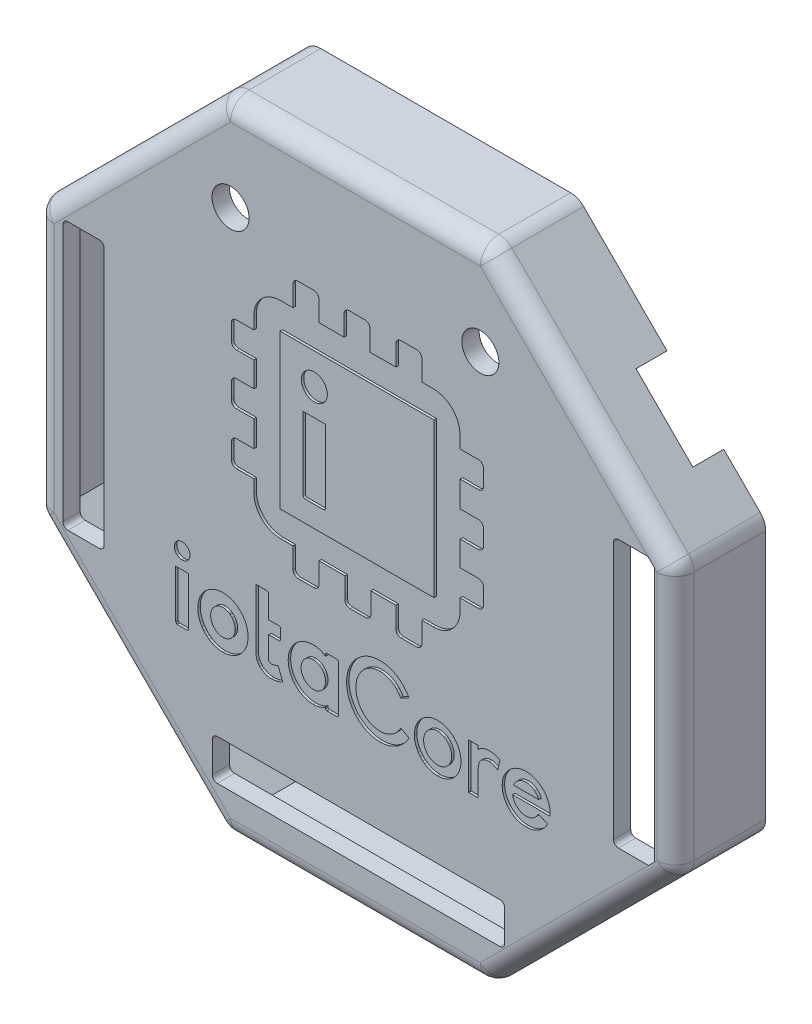
SolidWorks part; units mm, degrees
ref_plane "Front Plane" through (0, 0, 0) normal (0, 0, 1) x (1, 0, 0)
ref_plane "Top Plane" through (0, 0, 0) normal (0, 1, 0) x (1, 0, 0)
ref_plane "Right Plane" through (0, 0, 0) normal (1, 0, 0) x (0, 0, -1)
sketch "Sketch1" plane through (0, 0, 0) normal (0, 0, 1) x (1, 0, 0)
  line L0 (25.9, -10.1068) -> (25.9, 10.1068) construction
  line L1 (25.4607, 11.1675) -> (22.5059, 14.1222) construction
  line L2 (22.5059, 14.1222) -> (21.5159, 13.1323) construction
  line L3 (21.5159, 13.1323) -> (24.5, 10.1482) construction
  line L4 (24.5, 10.1482) -> (24.5, -10.1482) construction
  line L5 (24.5, -10.1482) -> (21.6927, -12.9555) construction
  line L6 (21.6927, -12.9555) -> (22.6827, -13.9455) construction
  line L7 (22.6827, -13.9455) -> (25.4607, -11.1675) construction
  line L8 (-16.1773, -20.4508) -> (-11.1675, -25.4607) construction
  line L9 (-10.1068, -25.9) -> (10.1068, -25.9) construction
  line L10 (11.1675, -25.4607) -> (15.6116, -21.0165) construction
  line L11 (15.6116, -21.0165) -> (14.6216, -20.0266) construction
  line L12 (14.6216, -20.0266) -> (10.1482, -24.5) construction
  line L13 (10.1482, -24.5) -> (-10.1482, -24.5) construction
  line L14 (-10.1482, -24.5) -> (-15.1873, -19.4609) construction
  line L15 (-15.1873, -19.4609) -> (-16.1773, -20.4508) construction
  line L16 (-22.117, 14.5112) -> (-25.4607, 11.1675) construction
  line L17 (-25.9, 10.1068) -> (-25.9, -10.1068) construction
  line L18 (-25.4607, -11.1675) -> (-22.1877, -14.4404) construction
  line L19 (-22.1877, -14.4404) -> (-21.1977, -13.4505) construction
  line L20 (-21.1977, -13.4505) -> (-24.5, -10.1482) construction
  line L21 (-24.5, -10.1482) -> (-24.5, 10.1482) construction
  line L22 (-24.5, 10.1482) -> (-21.127, 13.5212) construction
  line L23 (-21.127, 13.5212) -> (-22.117, 14.5112) construction
  line L24 (10.1068, 25.9) -> (-10.1068, 25.9) construction
  line L25 (-11.1675, 25.4607) -> (-17.5208, 19.1073) construction
  line L26 (-17.5208, 19.1073) -> (-16.5308, 18.1174) construction
  line L27 (-16.5308, 18.1174) -> (-10.1482, 24.5) construction
  line L28 (-10.1482, 24.5) -> (10.1482, 24.5) construction
  line L29 (10.1482, 24.5) -> (16.9197, 17.7285) construction
  line L30 (16.9197, 17.7285) -> (17.9097, 18.7184) construction
  line L31 (17.9097, 18.7184) -> (11.1675, 25.4607) construction
  line L32 (25.9, -10.1068) -> (25.9, 10.1068)
  line L33 (25.4607, 11.1675) -> (22.5059, 14.1222)
  line L34 (22.5059, 14.1222) -> (21.5159, 13.1323)
  line L35 (21.5159, 13.1323) -> (24.5, 10.1482)
  line L36 (24.5, 10.1482) -> (24.5, -10.1482)
  line L37 (24.5, -10.1482) -> (21.6927, -12.9555)
  line L38 (21.6927, -12.9555) -> (22.6827, -13.9455)
  line L39 (22.6827, -13.9455) -> (25.4607, -11.1675)
  line L40 (-16.1773, -20.4508) -> (-11.1675, -25.4607)
  line L41 (-10.1068, -25.9) -> (10.1068, -25.9)
  line L42 (11.1675, -25.4607) -> (15.6116, -21.0165)
  line L43 (15.6116, -21.0165) -> (14.6216, -20.0266)
  line L44 (14.6216, -20.0266) -> (10.1482, -24.5)
  line L45 (10.1482, -24.5) -> (-10.1482, -24.5)
  line L46 (-10.1482, -24.5) -> (-15.1873, -19.4609)
  line L47 (-15.1873, -19.4609) -> (-16.1773, -20.4508)
  line L48 (-22.117, 14.5112) -> (-25.4607, 11.1675)
  line L49 (-25.9, 10.1068) -> (-25.9, -10.1068)
  line L50 (-25.4607, -11.1675) -> (-22.1877, -14.4404)
  line L51 (-22.1877, -14.4404) -> (-21.1977, -13.4505)
  line L52 (-21.1977, -13.4505) -> (-24.5, -10.1482)
  line L53 (-24.5, -10.1482) -> (-24.5, 10.1482)
  line L54 (-24.5, 10.1482) -> (-21.127, 13.5212)
  line L55 (-21.127, 13.5212) -> (-22.117, 14.5112)
  line L56 (10.1068, 25.9) -> (-10.1068, 25.9)
  line L57 (-11.1675, 25.4607) -> (-17.5208, 19.1073)
  line L58 (-17.5208, 19.1073) -> (-16.5308, 18.1174)
  line L59 (-16.5308, 18.1174) -> (-10.1482, 24.5)
  line L60 (-10.1482, 24.5) -> (10.1482, 24.5)
  line L61 (10.1482, 24.5) -> (16.9197, 17.7285)
  line L62 (16.9197, 17.7285) -> (17.9097, 18.7184)
  line L63 (17.9097, 18.7184) -> (11.1675, 25.4607)
  line L66 (-17.5208, 19.1073) -> (-16.5308, 18.1174)
  line L67 (-21.127, 13.5212) -> (-22.117, 14.5112)
  arc A0 (25.9, 10.1068) -> (25.4607, 11.1675) centre (24.4, 10.1068) ccw construction
  arc A1 (25.4607, -11.1675) -> (25.9, -10.1068) centre (24.4, -10.1068) ccw construction
  arc A2 (-11.1675, -25.4607) -> (-10.1068, -25.9) centre (-10.1068, -24.4) ccw construction
  arc A3 (10.1068, -25.9) -> (11.1675, -25.4607) centre (10.1068, -24.4) ccw construction
  arc A4 (-25.4607, 11.1675) -> (-25.9, 10.1068) centre (-24.4, 10.1068) ccw construction
  arc A5 (-25.9, -10.1068) -> (-25.4607, -11.1675) centre (-24.4, -10.1068) ccw construction
  arc A6 (-10.1068, 25.9) -> (-11.1675, 25.4607) centre (-10.1068, 24.4) ccw construction
  arc A7 (11.1675, 25.4607) -> (10.1068, 25.9) centre (10.1068, 24.4) ccw construction
  arc A8 (25.9, 10.1068) -> (25.4607, 11.1675) centre (24.4, 10.1068) ccw
  arc A9 (25.4607, -11.1675) -> (25.9, -10.1068) centre (24.4, -10.1068) ccw
  arc A10 (-11.1675, -25.4607) -> (-10.1068, -25.9) centre (-10.1068, -24.4) ccw
  arc A11 (10.1068, -25.9) -> (11.1675, -25.4607) centre (10.1068, -24.4) ccw
  arc A12 (-25.4607, 11.1675) -> (-25.9, 10.1068) centre (-24.4, 10.1068) ccw
  arc A13 (-25.9, -10.1068) -> (-25.4607, -11.1675) centre (-24.4, -10.1068) ccw
  arc A14 (-10.1068, 25.9) -> (-11.1675, 25.4607) centre (-10.1068, 24.4) ccw
  arc A15 (11.1675, 25.4607) -> (10.1068, 25.9) centre (10.1068, 24.4) ccw
extrude "Boss-Extrude1" add sketch "Sketch1" along normal blind 5 contours L63 A15 L56 A14 L57 L58 L59 L60 L61 L62 | L49 A13 L50 L51 L52 L53 L54 L55 L48 A12 | L41 A11 L42 L43 L44 L45 L46 L47 L40 A10 | L39 A9 L32 A8 L33 L34 L35 L36 L37 L38 region at (24.747, 0.1144, 0) region at (-15.453, -20.1852, 0) region at (-24.631, 0.0454, 0) region at (10.5417, 25.4499, 0)
sketch "Sketch2" plane through (0, 0, 5) normal (0, 0, 1) x (1, 0, 0)
  line L0 (22.6827, -13.9455) -> (25.4607, -11.1675) construction
  line L1 (25.9, -10.1068) -> (25.9, 10.1068) construction
  line L2 (25.4607, 11.1675) -> (22.5059, 14.1222) construction
  line L3 (22.5059, 14.1222) -> (21.5159, 13.1323) construction
  line L4 (21.5159, 13.1323) -> (24.5, 10.1482) construction
  line L5 (24.5, 10.1482) -> (24.5, -10.1482) construction
  line L6 (24.5, -10.1482) -> (21.6927, -12.9555) construction
  line L7 (21.6927, -12.9555) -> (22.6827, -13.9455) construction
  line L8 (-10.1068, -25.9) -> (10.1068, -25.9) construction
  line L9 (11.1675, -25.4607) -> (15.6116, -21.0165) construction
  line L10 (15.6116, -21.0165) -> (14.6216, -20.0266) construction
  line L11 (14.6216, -20.0266) -> (10.1482, -24.5) construction
  line L12 (10.1482, -24.5) -> (-10.1482, -24.5) construction
  line L13 (-10.1482, -24.5) -> (-15.1873, -19.4609) construction
  line L14 (-15.1873, -19.4609) -> (-16.1773, -20.4508) construction
  line L15 (-16.1773, -20.4508) -> (-11.1675, -25.4607) construction
  line L16 (-25.9, 10.1068) -> (-25.9, -10.1068) construction
  line L17 (-25.4607, -11.1675) -> (-22.1877, -14.4404) construction
  line L18 (-22.1877, -14.4404) -> (-21.1977, -13.4505) construction
  line L19 (-21.1977, -13.4505) -> (-24.5, -10.1482) construction
  line L20 (-24.5, -10.1482) -> (-24.5, 10.1482) construction
  line L21 (-24.5, 10.1482) -> (-21.127, 13.5212) construction
  line L22 (-21.127, 13.5212) -> (-22.117, 14.5112) construction
  line L23 (-22.117, 14.5112) -> (-25.4607, 11.1675) construction
  line L24 (17.9097, 18.7184) -> (11.1675, 25.4607) construction
  line L25 (10.1068, 25.9) -> (-10.1068, 25.9) construction
  line L26 (-11.1675, 25.4607) -> (-17.5208, 19.1073) construction
  line L27 (-17.5208, 19.1073) -> (-16.5308, 18.1174) construction
  line L28 (-16.5308, 18.1174) -> (-10.1482, 24.5) construction
  line L29 (-10.1482, 24.5) -> (10.1482, 24.5) construction
  line L30 (10.1482, 24.5) -> (16.9197, 17.7285) construction
  line L31 (16.9197, 17.7285) -> (17.9097, 18.7184) construction
  line L32 (22.6827, -13.9455) -> (25.4607, -11.1675)
  line L33 (25.9, -10.1068) -> (25.9, 10.1068)
  line L34 (25.4607, 11.1675) -> (22.5059, 14.1222)
  line L35 (22.5059, 14.1222) -> (21.5159, 13.1323)
  line L36 (21.5159, 13.1323) -> (24.5, 10.1482)
  line L37 (24.5, 10.1482) -> (24.5, -10.1482)
  line L38 (24.5, -10.1482) -> (21.6927, -12.9555)
  line L39 (21.6927, -12.9555) -> (22.6827, -13.9455)
  line L40 (-10.1068, -25.9) -> (10.1068, -25.9)
  line L41 (11.1675, -25.4607) -> (15.6116, -21.0165)
  line L42 (15.6116, -21.0165) -> (14.6216, -20.0266)
  line L43 (14.6216, -20.0266) -> (10.1482, -24.5)
  line L44 (10.1482, -24.5) -> (-10.1482, -24.5)
  line L45 (-10.1482, -24.5) -> (-15.1873, -19.4609)
  line L46 (-15.1873, -19.4609) -> (-16.1773, -20.4508)
  line L47 (-16.1773, -20.4508) -> (-11.1675, -25.4607)
  line L48 (-25.9, 10.1068) -> (-25.9, -10.1068)
  line L49 (-25.4607, -11.1675) -> (-22.1877, -14.4404)
  line L50 (-22.1877, -14.4404) -> (-21.1977, -13.4505)
  line L51 (-21.1977, -13.4505) -> (-24.5, -10.1482)
  line L52 (-24.5, -10.1482) -> (-24.5, 10.1482)
  line L53 (-24.5, 10.1482) -> (-21.127, 13.5212)
  line L54 (-21.127, 13.5212) -> (-22.117, 14.5112)
  line L55 (-22.117, 14.5112) -> (-25.4607, 11.1675)
  line L56 (17.9097, 18.7184) -> (11.1675, 25.4607)
  line L57 (10.1068, 25.9) -> (-10.1068, 25.9)
  line L58 (-11.1675, 25.4607) -> (-17.5208, 19.1073)
  line L59 (-17.5208, 19.1073) -> (-16.5308, 18.1174)
  line L60 (-16.5308, 18.1174) -> (-10.1482, 24.5)
  line L61 (-10.1482, 24.5) -> (10.1482, 24.5)
  line L62 (10.1482, 24.5) -> (16.9197, 17.7285)
  line L63 (16.9197, 17.7285) -> (17.9097, 18.7184)
  line L64 (-22.117, 14.5112) -> (-17.5208, 19.1073)
  line L65 (-16.5308, 18.1174) -> (-21.127, 13.5212)
  line L66 (-21.1977, -13.4505) -> (-15.1873, -19.4609)
  line L67 (-16.1773, -20.4508) -> (-22.1877, -14.4404)
  line L68 (14.6216, -20.0266) -> (21.6927, -12.9555)
  line L69 (22.6827, -13.9455) -> (15.6116, -21.0165)
  line L70 (22.5059, 14.1222) -> (17.9097, 18.7184)
  line L71 (21.5159, 13.1323) -> (16.9197, 17.7285)
  arc A0 (25.4607, -11.1675) -> (25.9, -10.1068) centre (24.4, -10.1068) ccw construction
  arc A1 (25.9, 10.1068) -> (25.4607, 11.1675) centre (24.4, 10.1068) ccw construction
  arc A2 (10.1068, -25.9) -> (11.1675, -25.4607) centre (10.1068, -24.4) ccw construction
  arc A3 (-11.1675, -25.4607) -> (-10.1068, -25.9) centre (-10.1068, -24.4) ccw construction
  arc A4 (-25.9, -10.1068) -> (-25.4607, -11.1675) centre (-24.4, -10.1068) ccw construction
  arc A5 (-25.4607, 11.1675) -> (-25.9, 10.1068) centre (-24.4, 10.1068) ccw construction
  arc A6 (11.1675, 25.4607) -> (10.1068, 25.9) centre (10.1068, 24.4) ccw construction
  arc A7 (-10.1068, 25.9) -> (-11.1675, 25.4607) centre (-10.1068, 24.4) ccw construction
  arc A8 (25.4607, -11.1675) -> (25.9, -10.1068) centre (24.4, -10.1068) ccw
  arc A9 (25.9, 10.1068) -> (25.4607, 11.1675) centre (24.4, 10.1068) ccw
  arc A10 (10.1068, -25.9) -> (11.1675, -25.4607) centre (10.1068, -24.4) ccw
  arc A11 (-11.1675, -25.4607) -> (-10.1068, -25.9) centre (-10.1068, -24.4) ccw
  arc A12 (-25.9, -10.1068) -> (-25.4607, -11.1675) centre (-24.4, -10.1068) ccw
  arc A13 (-25.4607, 11.1675) -> (-25.9, 10.1068) centre (-24.4, 10.1068) ccw
  arc A14 (11.1675, 25.4607) -> (10.1068, 25.9) centre (10.1068, 24.4) ccw
  arc A15 (-10.1068, 25.9) -> (-11.1675, 25.4607) centre (-10.1068, 24.4) ccw
  line M21 (17.9097, 18.7184) -> (11.1675, 25.4607)
  arc M22 (11.1675, 25.4607) -> (10.1068, 25.9) centre (10.1068, 24.4) ccw
  line M23 (10.1068, 25.9) -> (-10.1068, 25.9)
  arc M24 (-10.1068, 25.9) -> (-11.1675, 25.4607) centre (-10.1068, 24.4) ccw
  line M25 (-11.1675, 25.4607) -> (-17.5208, 19.1073)
  line M26 (-17.5208, 19.1073) -> (-16.5308, 18.1174)
  line M27 (-16.5308, 18.1174) -> (-10.1482, 24.5)
  line M28 (-10.1482, 24.5) -> (10.1482, 24.5)
  line M29 (10.1482, 24.5) -> (16.9197, 17.7285)
  line M30 (16.9197, 17.7285) -> (17.9097, 18.7184)
extrude "Boss-Extrude2" add sketch "Sketch2" along normal blind 1.4 contours L36 L71 L65 L53 L52 L51 L66 L45 L44 L43 L68 L38 L37 M29 M28 M27 | L33 A9 L34 L35 L36 L37 L38 L39 L32 A8 | L69 L39 L68 L42 | L47 A11 L40 A10 L41 L42 L43 L44 L45 L46 | L67 L46 L66 L50 | L55 A13 L48 A12 L49 L50 L51 L52 L53 L54 | L65 L64 L54 M26 | M30 M21 M22 M23 M24 M25 M26 M27 M28 M29 | L71 L35 L70 M30 region at (24.747, 0.1144, 5) region at (18.6522, -16.986, 5) region at (0, 0, 5) region at (13.1602, -23.0093, 5) region at (19.7128, 15.9254, 5) region at (13.7911, 21.3714, 5) region at (-18.6875, -16.9507, 5) region at (-24.631, 0.0454, 5) region at (-19.3239, 16.3143, 5)
sketch "Sketch3" plane through (0, 0, 5) normal (0, 0, -1) x (-1, 0, 0)
  line L0 (-21.5159, 13.1323) -> (-16.9197, 17.7285)
  line L1 (-16.9197, 17.7285) -> (-17.9097, 18.7184)
  line L2 (-17.9097, 18.7184) -> (-22.5059, 14.1222)
  line L3 (-22.5059, 14.1222) -> (-21.5159, 13.1323)
  line L4 (21.127, 13.5212) -> (16.5308, 18.1174)
  line L5 (16.5308, 18.1174) -> (17.5208, 19.1073)
  line L6 (17.5208, 19.1073) -> (22.117, 14.5112)
  line L7 (22.117, 14.5112) -> (21.127, 13.5212)
extrude "Boss-Extrude3" add sketch "Sketch3" along normal blind 3.4 contours L7 L4 L5 L6 | L3 L0 L1 L2
sketch "Sketch4" plane through (0, 0, 5) normal (0, 0, -1) x (-1, 0, 0)
  line L0 (-15.6116, -21.0165) -> (-14.6216, -20.0266)
  line L1 (-14.6216, -20.0266) -> (-21.6927, -12.9555)
  line L2 (-21.6927, -12.9555) -> (-22.6827, -13.9455)
  line L3 (-22.6827, -13.9455) -> (-15.6116, -21.0165)
extrude "Boss-Extrude4" add sketch "Sketch4" along normal blind 3.4
sketch "Sketch5" plane through (0, 0, 5) normal (0, 0, -1) x (-1, 0, 0)
  line L0 (16.1773, -20.4508) -> (22.1877, -14.4404)
  line L1 (22.1877, -14.4404) -> (21.1977, -13.4505)
  line L2 (21.1977, -13.4505) -> (15.1873, -19.4609)
  line L3 (15.1873, -19.4609) -> (16.1773, -20.4508)
extrude "Boss-Extrude5" add sketch "Sketch5" along normal blind 1
fillet "Fillet1" radius 1.5 18 edges at (10.6808, -25.7858, 6.4) (0, -25.9, 6.4) (-10.6808, -25.7858, 6.4) (-18.3141, -18.3141, 6.4) (-25.7858, -10.6808, 6.4) (-25.9, 0, 6.4) (-25.7858, 10.6808, 6.4) (-18.3141, 18.3141, 6.4) (-10.6808, 25.7858, 6.4) (0, 25.9, 6.4) (10.6808, 25.7858, 6.4) (18.3141, 18.3141, 6.4) (25.7858, 10.6808, 6.4) (25.9, 0, 6.4) (25.7858, -10.6808, 6.4) (18.3141, -18.3141, 6.4) (15.1166, -20.5216, 1.6) (22.1877, -13.4505, 1.6)
sketch "Sketch6" plane through (0, 0, 6.4) normal (0, 0, 1) x (1, 0, 0)
  line L0 (-23.2729, -10.394) -> (-20.7329, -10.394) construction
  line L1 (-23.2729, 10.434) -> (-23.2729, -10.394) construction
  line L2 (-20.7329, -10.394) -> (-20.7329, 10.434) construction
  line L3 (-20.7329, 10.434) -> (-23.2729, 10.434) construction
  line L4 (21.2779, -10.389) -> (23.8179, -10.389) construction
  line L5 (23.8179, -10.389) -> (23.8179, 10.439) construction
  line L6 (21.2779, 10.439) -> (21.2779, -10.389) construction
  line L7 (23.8179, 10.439) -> (21.2779, 10.439) construction
  line L8 (-23.2729, -10.394) -> (-20.7329, -10.394)
  line L9 (-23.2729, 10.434) -> (-23.2729, -10.394)
  line L10 (-20.7329, -10.394) -> (-20.7329, 10.434)
  line L11 (-20.7329, 10.434) -> (-23.2729, 10.434)
  line L12 (21.2779, -10.389) -> (23.8179, -10.389)
  line L13 (23.8179, -10.389) -> (23.8179, 10.439)
  line L14 (21.2779, 10.439) -> (21.2779, -10.389)
  line L15 (23.8179, 10.439) -> (21.2779, 10.439)
  line L16 (-20.3329, -10.394) -> (-20.3329, 10.434)
  line L17 (-20.7329, 10.834) -> (-23.2729, 10.834)
  line L18 (-23.6729, 10.434) -> (-23.6729, -10.394)
  line L19 (-23.2729, -10.794) -> (-20.7329, -10.794)
  line L20 (21.2779, -10.789) -> (23.8179, -10.789)
  line L21 (24.2179, -10.389) -> (24.2179, 10.439)
  line L22 (23.8179, 10.839) -> (21.2779, 10.839)
  line L23 (20.8779, 10.439) -> (20.8779, -10.389)
  line L24 (24.2179, 10.839) -> (20.8779, 10.839) construction
  line L25 (20.8779, 10.839) -> (20.8779, -10.789) construction
  line L26 (24.2179, -10.789) -> (24.2179, 10.839) construction
  line L27 (20.8779, -10.789) -> (24.2179, -10.789) construction
  line L28 (-20.3329, -10.794) -> (-20.3329, 10.834) construction
  line L29 (-23.6729, -10.794) -> (-20.3329, -10.794) construction
  line L30 (-23.6729, 10.834) -> (-23.6729, -10.794) construction
  line L31 (-20.3329, 10.834) -> (-23.6729, 10.834) construction
  arc A0 (21.2779, 10.839) -> (20.8779, 10.439) centre (21.2779, 10.439) ccw
  arc A1 (24.2179, 10.439) -> (23.8179, 10.839) centre (23.8179, 10.439) ccw
  arc A2 (23.8179, -10.789) -> (24.2179, -10.389) centre (23.8179, -10.389) ccw
  arc A3 (21.2779, -10.789) -> (20.8779, -10.389) centre (21.2779, -10.389) cw
  arc A4 (-20.3329, -10.394) -> (-20.7329, -10.794) centre (-20.7329, -10.394) cw
  arc A5 (-23.6729, -10.394) -> (-23.2729, -10.794) centre (-23.2729, -10.394) ccw
  arc A6 (-20.3329, 10.434) -> (-20.7329, 10.834) centre (-20.7329, 10.434) ccw
  arc A7 (-23.2729, 10.834) -> (-23.6729, 10.434) centre (-23.2729, 10.434) ccw
  line M15 (10.1068, -24.4) -> (24.4, -10.1068)
  line M17 (24.4, 10.1068) -> (10.1068, 24.4)
  dimension "D2" = 0.4
  dimension "D1" = 0.4
extrude "Cut-Extrude1" cut sketch "Sketch6" against normal through all contours L10 L11 L9 L8 | L17 A7 L18 A5 L19 A4 L16 A6 L11 L10 L8 L9 | L13 L15 L14 L12 | A3 L20 L21 L22 A0 L23 L15 L13 L12 L14 M15 M17 region at (-22.0029, 0.02, 6.4) region at (22.5479, 0.025, 6.4) region at (-20.6048, -10.5221, 6.4) region at (21.1499, -10.5171, 6.4)
sketch "Sketch7" plane through (0, 0, 6.4) normal (0, 0, 1) x (1, 0, 0)
  line L0 (9.3915, -22.0846) -> (11.6775, -22.0846) construction
  line L1 (11.6775, -22.0846) -> (11.6775, -19.5954) construction
  line L2 (-11.1825, -22.0846) -> (-8.8965, -22.0846) construction
  line L3 (-11.1825, -19.5954) -> (-11.1825, -22.0846) construction
  line L4 (9.3915, -22.0846) -> (11.6775, -22.0846)
  line L5 (11.6775, -22.0846) -> (11.6775, -19.5954)
  line L6 (-11.1825, -22.0846) -> (-8.8965, -22.0846)
  line L7 (-11.1825, -19.5954) -> (-11.1825, -22.0846)
  line L8 (-11.1825, -19.5954) -> (11.6775, -19.5954)
  line L9 (9.3915, -22.0846) -> (-8.8965, -22.0846)
  line L10 (9.3915, -22.4846) -> (-8.8965, -22.4846)
  line L11 (-11.1825, -22.4846) -> (-8.8965, -22.4846)
  line L12 (-11.5825, -19.5954) -> (-11.5825, -22.0846)
  line L13 (-11.1825, -19.1954) -> (11.6775, -19.1954)
  line L14 (12.0775, -22.0846) -> (12.0775, -19.5954)
  line L15 (9.3915, -22.4846) -> (11.6775, -22.4846)
  line L16 (-11.5825, -19.1954) -> (12.0775, -19.1954) construction
  line L17 (12.0775, -22.4846) -> (12.0775, -19.1954) construction
  line L18 (9.3915, -22.4846) -> (12.0775, -22.4846) construction
  line L19 (-11.5825, -22.4846) -> (-8.8965, -22.4846) construction
  line L20 (-11.5825, -19.1954) -> (-11.5825, -22.4846) construction
  arc A0 (11.6775, -19.1954) -> (12.0775, -19.5954) centre (11.6775, -19.5954) cw
  arc A1 (12.0775, -22.0846) -> (11.6775, -22.4846) centre (11.6775, -22.0846) cw
  arc A2 (-11.1825, -22.4846) -> (-11.5825, -22.0846) centre (-11.1825, -22.0846) cw
  arc A3 (-11.5825, -19.5954) -> (-11.1825, -19.1954) centre (-11.1825, -19.5954) cw
  dimension "D2" = 0.4
  dimension "D1" = 0.4
extrude "Cut-Extrude2" cut sketch "Sketch7" against normal through all contours L9 L4 L5 L8 L7 L6 | A3 L12 A2 L11 L10 L15 A1 L14 A0 L13 L4 L9 L6 L7 L8 L5 | L9 L6 L7 L8 L5 L4 | L10 L11 A2 L12 A3 L13 A0 L14 A1 L15 region at (0.2475, -20.84, 6.4) region at (0.2475, -22.2457, 6.4)
sketch "Sketch10" plane through (0, 0, 6.4) normal (0, 0, 1) x (1, 0, 0)
  line L0 (6.3526, -0.709) -> (-6.1073, -0.709)
  line L1 (-6.1073, -0.709) -> (-6.1073, 11.751)
  line L2 (-6.1073, 11.751) -> (6.3526, 11.751)
  line L3 (6.3526, 11.751) -> (6.3526, -0.709)
  line L4 (10.3637, 9.084) -> (10.3637, 10.3555)
  line L5 (9.9467, 10.7717) -> (8.4679, 10.7717)
  line L6 (8.4679, 10.7717) -> (8.4679, 11.7461)
  line L7 (6.3004, 13.9128) -> (5.3733, 13.9128)
  line L8 (5.3733, 13.9128) -> (5.3733, 15.5588)
  line L9 (4.9563, 15.9758) -> (3.6857, 15.9758)
  line L10 (3.2686, 15.5588) -> (3.2686, 13.9128)
  line L11 (3.2686, 13.9128) -> (1.1746, 13.9128)
  line L12 (1.1746, 13.9128) -> (1.1746, 15.5588)
  line L13 (0.7584, 15.9758) -> (-0.5131, 15.9758)
  line L14 (-0.9293, 15.5588) -> (-0.9293, 13.9128)
  line L15 (-0.9293, 13.9128) -> (-2.9507, 13.9128)
  line L16 (-2.9507, 13.9128) -> (-2.9507, 15.5588)
  line L17 (-3.3678, 15.9758) -> (-4.6384, 15.9758)
  line L18 (-5.0554, 15.5588) -> (-5.0554, 13.9128)
  line L19 (-5.0554, 13.9128) -> (-6.0551, 13.9128)
  line L20 (-8.2226, 11.7461) -> (-8.2226, 10.7717)
  line L21 (-8.2226, 10.7717) -> (-9.6287, 10.7717)
  line L22 (-10.0458, 10.3555) -> (-10.0458, 9.084)
  line L23 (-9.6287, 8.6678) -> (-8.2226, 8.6678)
  line L24 (-8.2226, 8.6678) -> (-8.2226, 6.6463)
  line L25 (-8.2226, 6.6463) -> (-9.6287, 6.6463)
  line L26 (-10.0458, 6.2293) -> (-10.0458, 4.9587)
  line L27 (-9.6287, 4.5417) -> (-8.2226, 4.5417)
  line L28 (-8.2226, 4.5417) -> (-8.2226, 2.4476)
  line L29 (-8.2226, 2.4476) -> (-9.6287, 2.4476)
  line L30 (-10.0458, 2.0314) -> (-10.0458, 0.7599)
  line L31 (-9.6287, 0.3437) -> (-8.2226, 0.3437)
  line L32 (-8.2226, 0.3437) -> (-8.2226, -0.6095)
  line L33 (-6.0551, -2.777) -> (-5.0554, -2.777)
  line L34 (-5.0554, -2.777) -> (-5.0554, -4.4434)
  line L35 (-4.6384, -4.8604) -> (-3.3678, -4.8604)
  line L36 (-2.9507, -4.4434) -> (-2.9507, -2.777)
  line L37 (-2.9507, -2.777) -> (-0.8567, -2.777)
  line L38 (-0.8567, -2.777) -> (-0.8567, -4.4434)
  line L39 (-0.4396, -4.8604) -> (0.831, -4.8604)
  line L40 (1.248, -4.4434) -> (1.248, -2.777)
  line L41 (1.248, -2.777) -> (3.2686, -2.777)
  line L42 (3.2686, -2.777) -> (3.2686, -4.4434)
  line L43 (3.6857, -4.8604) -> (4.9563, -4.8604)
  line L44 (5.3733, -4.4434) -> (5.3733, -2.777)
  line L45 (5.3733, -2.777) -> (6.3004, -2.777)
  line L46 (8.4679, -0.6095) -> (8.4679, 0.3437)
  line L47 (8.4679, 0.3437) -> (9.9467, 0.3437)
  line L48 (10.3637, 0.7599) -> (10.3637, 2.0314)
  line L49 (9.9467, 2.4476) -> (8.4679, 2.4476)
  line L50 (8.4679, 2.4476) -> (8.4679, 4.469)
  line L51 (8.4679, 4.469) -> (9.9467, 4.469)
  line L52 (10.3637, 4.8861) -> (10.3637, 6.1567)
  line L53 (9.9467, 6.5737) -> (8.4679, 6.5737)
  line L54 (8.4679, 6.5737) -> (8.4679, 8.6678)
  line L55 (8.4679, 8.6678) -> (9.9467, 8.6678)
  line L56 (-2.4121, 7.0577) -> (-2.4121, 1.1786)
  line L57 (-2.5949, 0.9966) -> (-4.0639, 0.9966)
  line L58 (-4.2459, 1.1786) -> (-4.2459, 7.0577)
  line L59 (-4.2459, 7.0577) -> (-2.4121, 7.0577)
  line L60 (-14.5424, -8.9455) -> (-13.4977, -8.9455)
  line L61 (-13.4977, -8.9455) -> (-13.4977, -12.8799)
  line L62 (-13.4977, -12.8799) -> (-13.5822, -12.9643)
  line L63 (-13.5822, -12.9643) -> (-13.6459, -12.9681)
  line L64 (-13.6459, -12.9681) -> (-14.455, -12.9681)
  line L65 (-14.455, -12.9681) -> (-14.5385, -12.8827)
  line L66 (-14.5385, -12.8827) -> (-14.5424, -12.8198)
  line L67 (-14.5424, -12.8198) -> (-14.5424, -8.9455)
  line L68 (-13.3848, -7.597) -> (-13.3848, -7.6205)
  line L69 (-13.5529, -8.0427) -> (-13.561, -8.0512)
  line L70 (-14.0085, -8.2442) -> (-14.0319, -8.2442)
  line L71 (-14.4569, -8.0698) -> (-14.4636, -8.0631)
  line L72 (-14.6556, -7.6244) -> (-14.6556, -7.5931)
  line L73 (-14.4729, -7.16) -> (-14.4615, -7.1491)
  line L74 (-14.4615, -7.1491) -> (-14.3878, -7.0868)
  line L75 (-14.0358, -6.9733) -> (-14.0045, -6.9733)
  line L76 (-13.5861, -7.1413) -> (-13.5777, -7.1494)
  line L77 (-10.1353, -10.1363) -> (-10.155, -10.1279)
  line L78 (-10.155, -10.1279) -> (-10.1658, -10.1173)
  line L79 (-11.5056, -10.3384) -> (-11.5158, -10.355)
  line L80 (-11.3171, -11.8101) -> (-11.308, -11.8164)
  line L81 (-9.731, -10.9843) -> (-9.731, -10.9723)
  line L82 (-10.7052, -13.0616) -> (-10.7404, -13.0616)
  line L83 (-11.8353, -12.727) -> (-11.8441, -12.721)
  line L84 (-12.7555, -11.0036) -> (-12.7555, -10.9452)
  line L85 (-12.1524, -9.4873) -> (-12.1438, -9.4789)
  line L86 (-9.2496, -9.5351) -> (-9.2455, -9.5393)
  line L87 (-5.8737, -12.7382) -> (-6.0038, -12.793)
  line L88 (-6.8004, -12.9678) -> (-6.8082, -12.9678)
  line L89 (-7.7454, -12.5779) -> (-7.7604, -12.5614)
  line L90 (-7.7604, -12.5614) -> (-7.8266, -12.4749)
  line L91 (-8.0594, -11.7521) -> (-8.0594, -6.9733)
  line L92 (-8.0594, -6.9733) -> (-7.1072, -6.9733)
  line L93 (-7.1072, -6.9733) -> (-7.0226, -7.0577)
  line L94 (-7.0226, -7.0577) -> (-7.0187, -7.1213)
  line L95 (-7.0187, -7.1213) -> (-7.0187, -8.942)
  line L96 (-7.0187, -8.942) -> (-6.1361, -8.942)
  line L97 (-6.1361, -8.942) -> (-6.0512, -9.0261)
  line L98 (-6.0512, -9.0261) -> (-6.0474, -9.09)
  line L99 (-6.0474, -9.09) -> (-6.0474, -9.8979)
  line L100 (-6.0474, -9.8979) -> (-6.1319, -9.9827)
  line L101 (-6.1319, -9.9827) -> (-6.1954, -9.9865)
  line L102 (-6.1954, -9.9865) -> (-7.0187, -9.9865)
  line L103 (-7.0187, -9.9865) -> (-7.0187, -11.7243)
  line L104 (-6.4276, -11.8375) -> (-6.2631, -11.7573)
  line L105 (-6.2631, -11.7573) -> (-5.8737, -12.7382)
  line L106 (-3.3843, -9.9317) -> (-3.4467, -9.9317)
  line L107 (-3.4544, -12.0171) -> (-3.3686, -12.0171)
  line L108 (-1.377, -9.038) -> (-1.377, -12.876)
  line L109 (-1.377, -12.876) -> (-1.4692, -12.9681)
  line L110 (-1.4692, -12.9681) -> (-2.309, -12.9681)
  line L111 (-2.309, -12.9681) -> (-2.4215, -12.8936)
  line L112 (-2.4215, -12.8936) -> (-2.4215, -12.7611)
  line L113 (-3.3998, -13.0616) -> (-3.4036, -13.0616)
  line L114 (-2.4215, -9.2039) -> (-2.4215, -9.0201)
  line L115 (-2.4215, -9.0201) -> (-2.309, -8.9455)
  line L116 (-2.309, -8.9455) -> (-1.4692, -8.9455)
  line L117 (-1.4692, -8.9455) -> (-1.377, -9.038)
  line L118 (4.3331, -11.5371) -> (4.3331, -11.5529)
  line L119 (-0.7141, -10.1572) -> (-0.7141, -10.134)
  line L120 (1.979, -7.2927) -> (1.9868, -7.2927)
  line L121 (1.9516, -12.2427) -> (2.0335, -12.2427)
  line L122 (3.6746, -11.1905) -> (4.3331, -11.5371)
  line L123 (7.7893, -11.1107) -> (7.7893, -11.0991)
  line L124 (6.671, -13.0439) -> (6.6358, -13.0439)
  line L125 (4.7648, -11.13) -> (4.7648, -11.0716)
  line L126 (11.6934, -9.4189) -> (11.6934, -9.4228)
  line L127 (10.8514, -9.953) -> (10.7892, -9.953)
  line L128 (9.9159, -11.2196) -> (9.9159, -12.9349)
  line L129 (9.9159, -12.9349) -> (9.9082, -12.9465)
  line L130 (9.9082, -12.9465) -> (9.179, -12.9465)
  line L131 (9.179, -12.9465) -> (9.1674, -12.9349)
  line L132 (9.1674, -12.9349) -> (9.1674, -9.2748)
  line L133 (9.1674, -9.2748) -> (9.179, -9.2671)
  line L134 (9.179, -9.2671) -> (9.9082, -9.2671)
  line L135 (9.9082, -9.2671) -> (9.9159, -9.2748)
  line L136 (9.9159, -9.2748) -> (9.9159, -9.5553)
  line L137 (10.7966, -9.1929) -> (10.8943, -9.1929)
  line L138 (12.8553, -10.4754) -> (12.7878, -10.6195)
  line L139 (12.7878, -10.6195) -> (14.8381, -10.6195)
  line L140 (14.8381, -10.6195) -> (14.8381, -10.6157)
  line L141 (15.7554, -11.1029) -> (15.7554, -11.22)
  line L142 (15.7385, -11.329) -> (12.7115, -11.329)
  line L143 (13.8193, -13.0439) -> (13.8021, -13.0439)
  line L144 (11.8745, -11.1107) -> (11.8745, -11.0952)
  line L145 (13.7515, -9.1577) -> (13.8741, -9.1577)
  spline S0 degree 3 poles (9.9467, 8.6678) (10.1768, 8.6678) (10.3637, 8.8539) (10.3637, 9.084) knots 0 0 0 0 1 1 1 1
  spline S1 degree 3 poles (10.3637, 10.3555) (10.3637, 10.5856) (10.1768, 10.7717) (9.9467, 10.7717) knots 2 2 2 2 3 3 3 3
  spline S2 degree 3 poles (8.4679, 11.7461) (8.4679, 12.9424) (7.4976, 13.9128) (6.3004, 13.9128) knots 5 5 5 5 6 6 6 6
  spline S3 degree 3 poles (5.3733, 15.5588) (5.3733, 15.7889) (5.1864, 15.9758) (4.9563, 15.9758) knots 8 8 8 8 9 9 9 9
  spline S4 degree 3 poles (3.6857, 15.9758) (3.4555, 15.9758) (3.2686, 15.7889) (3.2686, 15.5588) knots 10 10 10 10 11 11 11 11
  spline S5 degree 3 poles (1.1746, 15.5588) (1.1746, 15.7889) (0.9885, 15.9758) (0.7584, 15.9758) knots 14 14 14 14 15 15 15 15
  spline S6 degree 3 poles (-0.5131, 15.9758) (-0.7432, 15.9758) (-0.9293, 15.7889) (-0.9293, 15.5588) knots 16 16 16 16 17 17 17 17
  spline S7 degree 3 poles (-2.9507, 15.5588) (-2.9507, 15.7889) (-3.1376, 15.9758) (-3.3678, 15.9758) knots 20 20 20 20 21 21 21 21
  spline S8 degree 3 poles (-4.6384, 15.9758) (-4.8685, 15.9758) (-5.0554, 15.7889) (-5.0554, 15.5588) knots 22 22 22 22 23 23 23 23
  spline S9 degree 3 poles (-6.0551, 13.9128) (-7.2523, 13.9128) (-8.2226, 12.9424) (-8.2226, 11.7461) knots 25 25 25 25 26 26 26 26
  spline S10 degree 3 poles (-9.6287, 10.7717) (-9.8589, 10.7717) (-10.0458, 10.5856) (-10.0458, 10.3555) knots 28 28 28 28 29 29 29 29
  spline S11 degree 3 poles (-10.0458, 9.084) (-10.0458, 8.8539) (-9.8589, 8.6678) (-9.6287, 8.6678) knots 30 30 30 30 31 31 31 31
  spline S12 degree 3 poles (-9.6287, 6.6463) (-9.8589, 6.6463) (-10.0458, 6.4595) (-10.0458, 6.2293) knots 34 34 34 34 35 35 35 35
  spline S13 degree 3 poles (-10.0458, 4.9587) (-10.0458, 4.7286) (-9.8589, 4.5417) (-9.6287, 4.5417) knots 36 36 36 36 37 37 37 37
  spline S14 degree 3 poles (-9.6287, 2.4476) (-9.8589, 2.4476) (-10.0458, 2.2615) (-10.0458, 2.0314) knots 40 40 40 40 41 41 41 41
  spline S15 degree 3 poles (-10.0458, 0.7599) (-10.0458, 0.5298) (-9.8589, 0.3437) (-9.6287, 0.3437) knots 42 42 42 42 43 43 43 43
  spline S16 degree 3 poles (-8.2226, -0.6095) (-8.2226, -1.8067) (-7.2523, -2.777) (-6.0551, -2.777) knots 45 45 45 45 46 46 46 46
  spline S17 degree 3 poles (-5.0554, -4.4434) (-5.0554, -4.6736) (-4.8685, -4.8604) (-4.6384, -4.8604) knots 48 48 48 48 49 49 49 49
  spline S18 degree 3 poles (-3.3678, -4.8604) (-3.1376, -4.8604) (-2.9507, -4.6736) (-2.9507, -4.4434) knots 50 50 50 50 51 51 51 51
  spline S19 degree 3 poles (-0.8567, -4.4434) (-0.8567, -4.6736) (-0.6698, -4.8604) (-0.4396, -4.8604) knots 54 54 54 54 55 55 55 55
  spline S20 degree 3 poles (0.831, -4.8604) (1.0611, -4.8604) (1.248, -4.6736) (1.248, -4.4434) knots 56 56 56 56 57 57 57 57
  spline S21 degree 3 poles (3.2686, -4.4434) (3.2686, -4.6736) (3.4555, -4.8604) (3.6857, -4.8604) knots 60 60 60 60 61 61 61 61
  spline S22 degree 3 poles (4.9563, -4.8604) (5.1864, -4.8604) (5.3733, -4.6736) (5.3733, -4.4434) knots 62 62 62 62 63 63 63 63
  spline S23 degree 3 poles (6.3004, -2.777) (7.4976, -2.777) (8.4679, -1.8067) (8.4679, -0.6095) knots 65 65 65 65 66 66 66 66
  spline S24 degree 3 poles (9.9467, 0.3437) (10.1768, 0.3437) (10.3637, 0.5298) (10.3637, 0.7599) knots 68 68 68 68 69 69 69 69
  spline S25 degree 3 poles (10.3637, 2.0314) (10.3637, 2.2615) (10.1768, 2.4476) (9.9467, 2.4476) knots 70 70 70 70 71 71 71 71
  spline S26 degree 3 poles (9.9467, 4.469) (10.1768, 4.469) (10.3637, 4.6559) (10.3637, 4.8861) knots 74 74 74 74 75 75 75 75
  spline S27 degree 3 poles (10.3637, 6.1567) (10.3637, 6.3868) (10.1768, 6.5737) (9.9467, 6.5737) knots 76 76 76 76 77 77 77 77
  spline S28 degree 3 poles (-2.4121, 1.1786) (-2.4121, 1.0782) (-2.4937, 0.9966) (-2.5949, 0.9966) knots 1 1 1 1 2 2 2 2
  spline S29 degree 3 poles (-4.0639, 0.9966) (-4.1643, 0.9966) (-4.2459, 1.0782) (-4.2459, 1.1786) knots 3 3 3 3 4 4 4 4
  spline S30 degree 3 poles (-4.3813, 9.2195) (-4.3813, 9.8005) (-3.9104, 10.2722) (-2.7483, 10.2722) (-2.2766, 9.8005) (-2.2766, 9.2195) knots 2 2 2 2 3 3 4 4 4 4
  spline S31 degree 3 poles (-2.2766, 9.2195) (-2.2766, 8.6384) (-2.7483, 8.1675) (-3.9104, 8.1675) (-4.3813, 8.6384) (-4.3813, 9.2195) knots 0 0 0 0 1 1 2 2 2 2
  spline S32 degree 3 poles (-13.3848, -7.6205) (-13.3848, -7.7724) (-13.4413, -7.9144) (-13.5529, -8.0427) knots 1 1 1 1 2 2 2 2
  spline S33 degree 3 poles (-13.561, -8.0512) (-13.6923, -8.1791) (-13.8429, -8.2442) (-14.0085, -8.2442) knots 3 3 3 3 4 4 4 4
  spline S34 degree 3 poles (-14.0319, -8.2442) (-14.1883, -8.2442) (-14.3312, -8.1855) (-14.4569, -8.0698) knots 5 5 5 5 6 6 6 6
  spline S35 degree 3 poles (-14.4636, -8.0631) (-14.5315, -7.9918) (-14.5766, -7.9274) (-14.6019, -7.8662) knots 7 7 7 7 8 8 8 8
  spline S36 degree 3 poles (-14.6019, -7.8662) (-14.6369, -7.7868) (-14.6556, -7.7042) (-14.6556, -7.6244) knots 8 8 8 8 9 9 9 9
  spline S37 degree 3 poles (-14.6556, -7.5931) (-14.6556, -7.4366) (-14.594, -7.2911) (-14.4729, -7.16) knots 10 10 10 10 11 11 11 11
  spline S38 degree 3 poles (-14.3878, -7.0868) (-14.2734, -7.0116) (-14.1549, -6.9733) (-14.0358, -6.9733) knots 13 13 13 13 14 14 14 14
  spline S39 degree 3 poles (-14.0045, -6.9733) (-13.8549, -6.9733) (-13.7142, -7.0299) (-13.5861, -7.1413) knots 15 15 15 15 16 16 16 16
  spline S40 degree 3 poles (-13.5777, -7.1494) (-13.4497, -7.2809) (-13.3847, -7.4314) (-13.3848, -7.597) knots 17 17 17 17 18 18 18 18
  spline S41 degree 3 poles (-10.0042, -10.2597) (-10.0997, -10.1584) (-10.1318, -10.138) (-10.1353, -10.1363) knots 0 0 0 0 1 1 1 1
  spline S42 degree 3 poles (-10.1658, -10.1173) (-10.2021, -10.0871) (-10.2362, -10.0635) (-10.2668, -10.047) knots 3 3 3 3 4 4 4 4
  spline S43 degree 3 poles (-10.2668, -10.047) (-10.414, -9.9679) (-10.5681, -9.9278) (-10.7249, -9.9278) knots 4 4 4 4 5 5 5 5
  spline S44 degree 3 poles (-10.7249, -9.9278) (-10.9657, -9.9278) (-11.1816, -10.0164) (-11.3846, -10.1989) knots 5 5 5 5 6 6 6 6
  spline S45 degree 3 poles (-11.3846, -10.1989) (-11.4771, -10.2913) (-11.5006, -10.3293) (-11.5056, -10.3384) knots 6 6 6 6 7 7 7 7
  spline S46 degree 3 poles (-11.5158, -10.355) (-11.6497, -10.5416) (-11.7149, -10.7462) (-11.7149, -10.98) knots 8 8 8 8 9 9 9 9
  spline S47 degree 3 poles (-11.7149, -10.98) (-11.7149, -11.2321) (-11.6346, -11.455) (-11.4695, -11.6621) knots 9 9 9 9 10 10 10 10
  spline S48 degree 3 poles (-11.4695, -11.6621) (-11.3808, -11.7619) (-11.3356, -11.7981) (-11.3171, -11.8101) knots 10 10 10 10 11 11 11 11
  spline S49 degree 3 poles (-11.308, -11.8164) (-11.1269, -11.9539) (-10.9362, -12.0207) (-10.7249, -12.0207) knots 12 12 12 12 13 13 13 13
  spline S50 degree 3 poles (-10.7249, -12.0207) (-10.4655, -12.0207) (-10.2408, -11.9247) (-10.0385, -11.7268) knots 13 13 13 13 14 14 14 14
  spline S51 degree 3 poles (-10.0385, -11.7268) (-9.9611, -11.6448) (-9.9047, -11.5721) (-9.8745, -11.5141) knots 14 14 14 14 15 15 15 15
  spline S52 degree 3 poles (-9.8745, -11.5141) (-9.7787, -11.3407) (-9.731, -11.1636) (-9.731, -10.9843) knots 15 15 15 15 16 16 16 16
  spline S53 degree 3 poles (-9.731, -10.9723) (-9.731, -10.7069) (-9.8203, -10.4738) (-10.0042, -10.2597) knots 17 17 17 17 18 18 18 18
  spline S54 degree 3 poles (-8.6901, -10.98) (-8.6901, -11.3295) (-8.7757, -11.6695) (-8.9444, -11.9904) knots 0 0 0 0 1 1 1 1
  spline S55 degree 3 poles (-8.9444, -11.9904) (-9.0042, -12.0987) (-9.0835, -12.2144) (-9.1816, -12.3371) knots 1 1 1 1 2 2 2 2
  spline S56 degree 3 poles (-9.1816, -12.3371) (-9.2946, -12.4675) (-9.3821, -12.5547) (-9.4533, -12.6078) knots 2 2 2 2 3 3 3 3
  spline S57 degree 3 poles (-9.4533, -12.6078) (-9.5231, -12.6651) (-9.5948, -12.7171) (-9.6621, -12.7593) knots 3 3 3 3 4 4 4 4
  spline S58 degree 3 poles (-9.6621, -12.7593) (-9.9945, -12.9604) (-10.3449, -13.0616) (-10.7052, -13.0616) knots 4 4 4 4 5 5 5 5
  spline S59 degree 3 poles (-10.7404, -13.0616) (-11.1202, -13.0616) (-11.4887, -12.9491) (-11.8353, -12.727) knots 6 6 6 6 7 7 7 7
  spline S60 degree 3 poles (-11.8441, -12.721) (-11.909, -12.6725) (-11.967, -12.6264) (-12.0183, -12.5832) knots 8 8 8 8 9 9 9 9
  spline S61 degree 3 poles (-12.0183, -12.5832) (-12.1269, -12.4914) (-12.2048, -12.4134) (-12.256, -12.3455) knots 9 9 9 9 10 10 10 10
  spline S62 degree 3 poles (-12.256, -12.3455) (-12.3136, -12.2791) (-12.3678, -12.2066) (-12.417, -12.13) knots 10 10 10 10 11 11 11 11
  spline S63 degree 3 poles (-12.417, -12.13) (-12.4727, -12.0411) (-12.5202, -11.9542) (-12.5588, -11.8712) knots 11 11 11 11 12 12 12 12
  spline S64 degree 3 poles (-12.5588, -11.8712) (-12.6896, -11.5823) (-12.7555, -11.2908) (-12.7555, -11.0036) knots 12 12 12 12 13 13 13 13
  spline S65 degree 3 poles (-12.7555, -10.9452) (-12.7555, -10.633) (-12.6771, -10.3163) (-12.5223, -10.0041) knots 14 14 14 14 15 15 15 15
  spline S66 degree 3 poles (-12.5223, -10.0041) (-12.4775, -9.9169) (-12.4244, -9.829) (-12.3639, -9.7408) knots 15 15 15 15 16 16 16 16
  spline S67 degree 3 poles (-12.3639, -9.7408) (-12.3147, -9.6715) (-12.2459, -9.5889) (-12.1524, -9.4873) knots 16 16 16 16 17 17 17 17
  spline S68 degree 3 poles (-12.1438, -9.4789) (-12.0067, -9.3527) (-11.9132, -9.2757) (-11.8492, -9.2359) knots 18 18 18 18 19 19 19 19
  spline S69 degree 3 poles (-11.8492, -9.2359) (-11.5122, -9.0057) (-11.1322, -8.8872) (-10.7249, -8.8872) knots 19 19 19 19 20 20 20 20
  spline S70 degree 3 poles (-10.7249, -8.8872) (-10.2705, -8.8872) (-9.8499, -9.0352) (-9.4748, -9.327) knots 20 20 20 20 21 21 21 21
  spline S71 degree 3 poles (-9.4748, -9.327) (-9.4213, -9.3664) (-9.3466, -9.4353) (-9.2496, -9.5351) knots 21 21 21 21 22 22 22 22
  spline S72 degree 3 poles (-9.2455, -9.5393) (-9.0545, -9.7524) (-8.9165, -9.9756) (-8.8351, -10.2027) knots 23 23 23 23 24 24 24 24
  spline S73 degree 3 poles (-8.8351, -10.2027) (-8.7395, -10.4485) (-8.6904, -10.7114) (-8.6901, -10.98) knots 24 24 24 24 25 25 25 25
  spline S74 degree 3 poles (-6.0038, -12.793) (-6.0695, -12.8208) (-6.1739, -12.8556) (-6.323, -12.8996) knots 1 1 1 1 2 2 2 2
  spline S75 degree 3 poles (-6.323, -12.8996) (-6.503, -12.9453) (-6.6619, -12.9678) (-6.8004, -12.9678) knots 2 2 2 2 3 3 3 3
  spline S76 degree 3 poles (-6.8082, -12.9678) (-7.0847, -12.9678) (-7.3457, -12.883) (-7.5844, -12.7157) knots 4 4 4 4 5 5 5 5
  spline S77 degree 3 poles (-7.5844, -12.7157) (-7.6278, -12.6848) (-7.6802, -12.6401) (-7.7454, -12.5779) knots 5 5 5 5 6 6 6 6
  spline S78 degree 3 poles (-7.8266, -12.4749) (-7.875, -12.412) (-7.9135, -12.3483) (-7.9412, -12.2857) knots 8 8 8 8 9 9 9 9
  spline S79 degree 3 poles (-7.9412, -12.2857) (-8.0196, -12.1086) (-8.0594, -11.9289) (-8.0594, -11.7521) knots 9 9 9 9 10 10 10 10
  spline S80 degree 3 poles (-7.0187, -11.7243) (-7.0187, -11.8533) (-6.9708, -11.8772) (-6.9504, -11.8874) knots 23 23 23 23 24 24 24 24
  spline S81 degree 3 poles (-6.9504, -11.8874) (-6.8994, -11.9148) (-6.8526, -11.9271) (-6.8043, -11.9271) knots 24 24 24 24 25 25 25 25
  spline S82 degree 3 poles (-6.8043, -11.9271) (-6.7466, -11.9271) (-6.6347, -11.9117) (-6.4276, -11.8375) knots 25 25 25 25 26 26 26 26
  spline S83 degree 3 poles (-2.8874, -10.0871) (-3.0568, -9.9841) (-3.2242, -9.9317) (-3.3843, -9.9317) knots 0 0 0 0 1 1 1 1
  spline S84 degree 3 poles (-3.4467, -9.9317) (-3.7155, -9.9317) (-3.9549, -10.0554) (-4.1788, -10.3096) knots 2 2 2 2 3 3 3 3
  spline S85 degree 3 poles (-4.1788, -10.3096) (-4.3288, -10.5237) (-4.4015, -10.7406) (-4.4015, -10.9723) knots 3 3 3 3 4 4 4 4
  spline S86 degree 3 poles (-4.4015, -10.9723) (-4.4015, -11.3362) (-4.249, -11.6269) (-3.9352, -11.8621) knots 4 4 4 4 5 5 5 5
  spline S87 degree 3 poles (-3.9352, -11.8621) (-3.7636, -11.9648) (-3.6019, -12.0171) (-3.4544, -12.0171) knots 5 5 5 5 6 6 6 6
  spline S88 degree 3 poles (-3.3686, -12.0171) (-3.1545, -12.0171) (-2.9496, -11.9303) (-2.7425, -11.7521) knots 7 7 7 7 8 8 8 8
  spline S89 degree 3 poles (-2.7425, -11.7521) (-2.5267, -11.5295) (-2.4215, -11.2757) (-2.4215, -10.9765) knots 8 8 8 8 9 9 9 9
  spline S90 degree 3 poles (-2.4215, -10.9765) (-2.4215, -10.6042) (-2.5738, -10.3145) (-2.8874, -10.0871) knots 9 9 9 9 10 10 10 10
  spline S91 degree 3 poles (-2.4215, -12.7611) (-2.6965, -12.9607) (-3.0241, -13.0616) (-3.3998, -13.0616) knots 5 5 5 5 6 6 6 6
  spline S92 degree 3 poles (-3.4036, -13.0616) (-4.0139, -13.0616) (-4.5385, -12.8127) (-4.9628, -12.322) knots 7 7 7 7 8 8 8 8
  spline S93 degree 3 poles (-4.9628, -12.322) (-5.282, -11.9215) (-5.4422, -11.4701) (-5.4422, -10.9765) knots 8 8 8 8 9 9 9 9
  spline S94 degree 3 poles (-5.4422, -10.9765) (-5.4422, -10.362) (-5.204, -9.8283) (-4.7341, -9.3864) knots 9 9 9 9 10 10 10 10
  spline S95 degree 3 poles (-4.7341, -9.3864) (-4.3365, -9.0531) (-3.887, -8.8872) (-3.392, -8.8872) knots 10 10 10 10 11 11 11 11
  spline S96 degree 3 poles (-3.392, -8.8872) (-3.0301, -8.8872) (-2.7049, -8.9934) (-2.4215, -9.2039) knots 11 11 11 11 12 12 12 12
  spline S97 degree 3 poles (4.3331, -11.5529) (4.2449, -11.7164) (4.1278, -11.8894) (3.9822, -12.0711) knots 1 1 1 1 2 2 2 2
  spline S98 degree 3 poles (3.9822, -12.0711) (3.4159, -12.6895) (2.7507, -12.9989) (1.9868, -12.9989) knots 2 2 2 2 3 3 3 3
  spline S99 degree 3 poles (1.9868, -12.9989) (1.2281, -12.9989) (0.5656, -12.6948) (-0.0008, -12.0869) knots 3 3 3 3 4 4 4 4
  spline S100 degree 3 poles (-0.0008, -12.0869) (-0.4765, -11.5125) (-0.7141, -10.8695) (-0.7141, -10.1572) knots 4 4 4 4 5 5 5 5
  spline S101 degree 3 poles (-0.7141, -10.134) (-0.7141, -9.4144) (-0.4726, -8.7685) (0.0108, -8.1969) knots 6 6 6 6 7 7 7 7
  spline S102 degree 3 poles (0.0108, -8.1969) (0.5723, -7.594) (1.2281, -7.2927) (1.979, -7.2927) knots 7 7 7 7 8 8 8 8
  spline S103 degree 3 poles (1.9868, -7.2927) (2.7222, -7.2927) (3.3652, -7.5785) (3.9161, -8.1501) knots 9 9 9 9 10 10 10 10
  spline S104 degree 3 poles (3.9161, -8.1501) (4.1109, -8.3737) (4.2487, -8.5657) (4.3292, -8.7271) knots 10 10 10 10 11 11 11 11
  spline S105 degree 3 poles (4.3292, -8.7271) (4.3085, -8.7453) (4.0891, -8.8659) (3.6707, -9.0895) knots 11 11 11 11 12 12 12 12
  spline S106 degree 3 poles (3.6707, -9.0895) (3.6004, -8.9623) (3.4953, -8.8153) (3.355, -8.649) knots 12 12 12 12 13 13 13 13
  spline S107 degree 3 poles (3.355, -8.649) (2.9522, -8.2437) (2.4958, -8.0412) (1.9868, -8.0412) knots 13 13 13 13 14 14 14 14
  spline S108 degree 3 poles (1.9868, -8.0412) (1.4696, -8.0412) (1.0108, -8.2461) (0.6109, -8.6567) knots 14 14 14 14 15 15 15 15
  spline S109 degree 3 poles (0.6109, -8.6567) (0.2263, -9.0909) (0.034, -9.5859) (0.034, -10.1417) knots 15 15 15 15 16 16 16 16
  spline S110 degree 3 poles (0.034, -10.1417) (0.034, -10.7865) (0.2798, -11.336) (0.7707, -11.7906) knots 16 16 16 16 17 17 17 17
  spline S111 degree 3 poles (0.7707, -11.7906) (1.142, -12.0922) (1.5357, -12.2427) (1.9516, -12.2427) knots 17 17 17 17 18 18 18 18
  spline S112 degree 3 poles (2.0335, -12.2427) (2.4909, -12.2427) (2.9184, -12.0542) (3.316, -11.6777) knots 19 19 19 19 20 20 20 20
  spline S113 degree 3 poles (3.316, -11.6777) (3.4848, -11.4907) (3.6043, -11.3283) (3.6746, -11.1905) knots 20 20 20 20 21 21 21 21
  spline S114 degree 3 poles (7.7893, -11.0991) (7.7893, -10.8002) (7.687, -10.5313) (7.4817, -10.2922) knots 0 0 0 0 1 1 1 1
  spline S115 degree 3 poles (7.4817, -10.2922) (7.3931, -10.1983) (7.3337, -10.1453) (7.3024, -10.1323) knots 1 1 1 1 2 2 2 2
  spline S116 degree 3 poles (7.3024, -10.1323) (7.2581, -10.0957) (7.2166, -10.0672) (7.1776, -10.0465) knots 2 2 2 2 3 3 3 3
  spline S117 degree 3 poles (7.1776, -10.0465) (7.0085, -9.9554) (6.8331, -9.9101) (6.6513, -9.9101) knots 3 3 3 3 4 4 4 4
  spline S118 degree 3 poles (6.6513, -9.9101) (6.376, -9.9101) (6.124, -10.0127) (5.8951, -10.218) knots 4 4 4 4 5 5 5 5
  spline S119 degree 3 poles (5.8951, -10.218) (5.8146, -10.2985) (5.764, -10.3583) (5.7432, -10.3973) knots 5 5 5 5 6 6 6 6
  spline S120 degree 3 poles (5.7432, -10.3973) (5.5924, -10.6076) (5.5172, -10.8442) (5.5172, -11.1064) knots 6 6 6 6 7 7 7 7
  spline S121 degree 3 poles (5.5172, -11.1064) (5.5172, -11.3898) (5.6093, -11.6471) (5.7938, -11.8785) knots 7 7 7 7 8 8 8 8
  spline S122 degree 3 poles (5.7938, -11.8785) (5.8743, -11.9692) (5.9366, -12.0289) (5.9809, -12.0574) knots 8 8 8 8 9 9 9 9
  spline S123 degree 3 poles (5.9809, -12.0574) (6.1862, -12.2135) (6.4098, -12.2916) (6.6513, -12.2916) knots 9 9 9 9 10 10 10 10
  spline S124 degree 3 poles (6.6513, -12.2916) (6.9477, -12.2916) (7.2099, -12.1798) (7.4388, -11.9565) knots 10 10 10 10 11 11 11 11
  spline S125 degree 3 poles (7.4388, -11.9565) (7.5295, -11.8602) (7.5931, -11.7769) (7.6297, -11.7069) knots 11 11 11 11 12 12 12 12
  spline S126 degree 3 poles (7.6297, -11.7069) (7.7362, -11.5146) (7.7893, -11.316) (7.7893, -11.1107) knots 12 12 12 12 13 13 13 13
  spline S127 degree 3 poles (8.542, -11.1068) (8.542, -11.4341) (8.4625, -11.7484) (8.304, -12.05) knots 0 0 0 0 1 1 1 1
  spline S128 degree 3 poles (8.304, -12.05) (8.2495, -12.1488) (8.1757, -12.2564) (8.0818, -12.3735) knots 1 1 1 1 2 2 2 2
  spline S129 degree 3 poles (8.0818, -12.3735) (7.9806, -12.4905) (7.8986, -12.5725) (7.8364, -12.6189) knots 2 2 2 2 3 3 3 3
  spline S130 degree 3 poles (7.8364, -12.6189) (7.7661, -12.6762) (7.7, -12.7243) (7.6374, -12.7633) knots 3 3 3 3 4 4 4 4
  spline S131 degree 3 poles (7.6374, -12.7633) (7.3284, -12.9504) (7.006, -13.0439) (6.671, -13.0439) knots 4 4 4 4 5 5 5 5
  spline S132 degree 3 poles (6.6358, -13.0439) (6.2825, -13.0439) (5.9432, -12.9402) (5.6188, -12.7321) knots 6 6 6 6 7 7 7 7
  spline S133 degree 3 poles (5.6188, -12.7321) (5.5562, -12.6853) (5.5003, -12.6414) (5.4511, -12.5995) knots 7 7 7 7 8 8 8 8
  spline S134 degree 3 poles (5.4511, -12.5995) (5.3495, -12.5137) (5.2767, -12.441) (5.2327, -12.3812) knots 8 8 8 8 9 9 9 9
  spline S135 degree 3 poles (5.2327, -12.3812) (5.1782, -12.319) (5.1273, -12.2515) (5.0805, -12.1787) knots 9 9 9 9 10 10 10 10
  spline S136 degree 3 poles (5.0805, -12.1787) (5.0288, -12.0954) (4.9845, -12.0149) (4.9483, -11.9368) knots 10 10 10 10 11 11 11 11
  spline S137 degree 3 poles (4.9483, -11.9368) (4.826, -11.6668) (4.7648, -11.3975) (4.7648, -11.13) knots 11 11 11 11 12 12 12 12
  spline S138 degree 3 poles (4.7648, -11.0716) (4.7648, -10.7809) (4.8376, -10.4884) (4.9831, -10.1948) knots 13 13 13 13 14 14 14 14
  spline S139 degree 3 poles (4.9831, -10.1948) (5.025, -10.114) (5.0742, -10.0324) (5.1315, -9.9491) knots 14 14 14 14 15 15 15 15
  spline S140 degree 3 poles (5.1315, -9.9491) (5.1754, -9.8865) (5.2419, -9.8074) (5.3301, -9.7114) knots 15 15 15 15 16 16 16 16
  spline S141 degree 3 poles (5.3301, -9.7114) (5.4574, -9.5944) (5.5484, -9.5191) (5.6029, -9.485) knots 16 16 16 16 17 17 17 17
  spline S142 degree 3 poles (5.6029, -9.485) (5.9225, -9.2671) (6.272, -9.1577) (6.6513, -9.1577) knots 17 17 17 17 18 18 18 18
  spline S143 degree 3 poles (6.6513, -9.1577) (7.0749, -9.1577) (7.4624, -9.2941) (7.8129, -9.5669) knots 18 18 18 18 19 19 19 19
  spline S144 degree 3 poles (7.8129, -9.5669) (7.8621, -9.6035) (7.9324, -9.6682) (8.0234, -9.7621) knots 19 19 19 19 20 20 20 20
  spline S145 degree 3 poles (8.0234, -9.7621) (8.2027, -9.9621) (8.33, -10.1674) (8.4052, -10.3776) knots 20 20 20 20 21 21 21 21
  spline S146 degree 3 poles (8.4052, -10.3776) (8.4963, -10.6118) (8.5416, -10.8547) (8.542, -11.1068) knots 21 21 21 21 22 22 22 22
  spline S147 degree 3 poles (11.6934, -9.4228) (11.5841, -9.9164) (11.5243, -10.1751) (11.5141, -10.1983) knots 1 1 1 1 2 2 2 2
  spline S148 degree 3 poles (11.5141, -10.1983) (11.2645, -10.0349) (11.0437, -9.953) (10.8514, -9.953) knots 2 2 2 2 3 3 3 3
  spline S149 degree 3 poles (10.7892, -9.953) (10.5396, -9.953) (10.3199, -10.0451) (10.1304, -10.2296) knots 4 4 4 4 5 5 5 5
  spline S150 degree 3 poles (10.1304, -10.2296) (9.9873, -10.4037) (9.9159, -10.7338) (9.9159, -11.2196) knots 5 5 5 5 6 6 6 6
  spline S151 degree 3 poles (9.9159, -9.5553) (10.2017, -9.3138) (10.4953, -9.1929) (10.7966, -9.1929) knots 15 15 15 15 16 16 16 16
  spline S152 degree 3 poles (10.8943, -9.1929) (11.1513, -9.1929) (11.4178, -9.2681) (11.6934, -9.4189) knots 17 17 17 17 18 18 18 18
  spline S153 degree 3 poles (14.8381, -10.6157) (14.7903, -10.4831) (14.6803, -10.3323) (14.5084, -10.1635) knots 0 0 0 0 1 1 1 1
  spline S154 degree 3 poles (14.5084, -10.1635) (14.2939, -9.9944) (14.0601, -9.9101) (13.8066, -9.9101) knots 1 1 1 1 2 2 2 2
  spline S155 degree 3 poles (13.8066, -9.9101) (13.4203, -9.9101) (13.1032, -10.0985) (12.8553, -10.4754) knots 2 2 2 2 3 3 3 3
  spline S156 degree 3 poles (15.7554, -11.22) (15.7554, -11.2928) (15.7497, -11.329) (15.7385, -11.329) knots 1 1 1 1 2 2 2 2
  spline S157 degree 3 poles (12.7115, -11.329) (12.7762, -11.6071) (12.8834, -11.8148) (13.0329, -11.9526) knots 3 3 3 3 4 4 4 4
  spline S158 degree 3 poles (13.0329, -11.9526) (13.261, -12.1787) (13.5205, -12.2916) (13.8109, -12.2916) knots 4 4 4 4 5 5 5 5
  spline S159 degree 3 poles (13.8109, -12.2916) (14.1772, -12.2916) (14.4845, -12.1214) (14.7323, -11.7811) knots 5 5 5 5 6 6 6 6
  spline S160 degree 3 poles (14.7323, -11.7811) (14.7801, -11.6953) (14.8086, -11.651) (14.817, -11.6485) knots 6 6 6 6 7 7 7 7
  spline S161 degree 3 poles (14.817, -11.6485) (15.3015, -11.851) (15.5469, -11.9551) (15.5525, -11.9604) knots 7 7 7 7 8 8 8 8
  spline S162 degree 3 poles (15.5525, -11.9604) (15.5131, -12.0514) (15.4242, -12.1878) (15.2864, -12.3696) knots 8 8 8 8 9 9 9 9
  spline S163 degree 3 poles (15.2864, -12.3696) (14.8719, -12.8192) (14.3829, -13.0439) (13.8193, -13.0439) knots 9 9 9 9 10 10 10 10
  spline S164 degree 3 poles (13.8021, -13.0439) (13.2216, -13.0439) (12.7228, -12.8062) (12.3058, -12.3306) knots 11 11 11 11 12 12 12 12
  spline S165 degree 3 poles (12.3058, -12.3306) (12.0182, -11.959) (11.8745, -11.5526) (11.8745, -11.1107) knots 12 12 12 12 13 13 13 13
  spline S166 degree 3 poles (11.8745, -11.0952) (11.8745, -10.487) (12.1265, -9.9726) (12.6314, -9.5515) knots 14 14 14 14 15 15 15 15
  spline S167 degree 3 poles (12.6314, -9.5515) (13.0033, -9.2892) (13.3767, -9.1577) (13.7515, -9.1577) knots 15 15 15 15 16 16 16 16
  spline S168 degree 3 poles (13.8741, -9.1577) (14.2855, -9.1577) (14.6817, -9.31) (15.0621, -9.6137) knots 17 17 17 17 18 18 18 18
  spline S169 degree 3 poles (15.0621, -9.6137) (15.2481, -9.7828) (15.3764, -9.9283) (15.4467, -10.0503) knots 18 18 18 18 19 19 19 19
  spline S170 degree 3 poles (15.4467, -10.0503) (15.6527, -10.3854) (15.7554, -10.7362) (15.7554, -11.1029) knots 19 19 19 19 20 20 20 20
extrude "Cut-Extrude3" cut sketch "Sketch10" against normal blind 0.2 contours L52 S27 L53 L54 L55 S0 L4 S1 L5 L6 S2 L7 L8 S3 L9 S4 L10 L11 L12 S5 L13 S6 L14 L15 L16 S7 L17 S8 L18 L19 S9 L20 L21 S10 L22 S11 L23 L24 L25 S12 L26 S13 L27 L28 L29 S14 L30 S15 L31 L32 S16 | S29 L57 S28 L56 L59 L58 | S31 S30 | S82 S81 S80 L103 L102 L101 L100 L99 L98 L97 L96 L95 L94 L93 L92 L91 S79 S78 L90 L89 S77 S76 L88 S75 S74 L87 L105 L104 | S73 S72 L86 S71 S70 S69 S68 L85 S67 S66 S65 L84 S64 S63 S62 S61 S60 L83 S59 L82 S58 S57 S56 S55 S54 S53 L81 S52 S51 S50 S49 L80 S48 S47 S46 L79 S45 S44 S43 S42 L78 L77 S41 | L67 L66 L65 L64 L63 L62 L61 L60 | S40 L76 S39 L75 S38 L74 L73 S37 L72 S36 S35 L71 S34 L70 S33 L69 S32 L68 | S96 S95 S94 S93 S92 L113 S91 L112 L111 L110 L109 L108 L117 L116 L115 L114 S90 S89 S88 L107 S87 S86 S85 S84 L106 S83 | S113 S112 L121 S111 S110 S109 S108 S107 S106 S105 S104 S103 L120 S102 S101 L119 S100 S99 S98 S97 L118 L122 | S170 S169 S168 L145 S167 S166 L144 S165 S164 L143 S163 S162 S161 S160 S159 S158 S157 L142 S156 L141 S155 S154 S153 L140 L139 L138 | S152 L137 S151 L136 L135 L134 L133 L132 L131 L130 L129 L128 S150 S149 L127 S148 S147 L126 | S146 S145 S144 S143 S142 S141 S140 S139 S138 L125 S137 S136 S135 S134 S133 S132 L124 S131 S130 S129 S128 S127 S126 S125 S124 S123 S122 S121 S120 S119 S118 S117 S116 S115 S114 L123 region at (10.0355, 8.9961, 6.4) region at (-3.329, 4.031, 6.4) region at (-14.02, -10.953, 6.4) region at (-14.0199, -7.6084, 6.4) region at (-10.7228, -13.0034, 6.4) region at (-7.2719, -10.1168, 6.4) region at (-1.4353, -10.957, 6.4) region at (4.2569, -11.545, 6.4) region at (6.6534, -12.9897, 6.4) region at (9.9453, -10.6348, 6.4) region at (13.744, -11.0569, 6.4) region at (-3.3291, 9.2198, 6.4)
sketch "Sketch11" plane through (0, 0, 6.4) normal (0, 0, 1) x (1, 0, 0)
  line L0 (-10.1068, 24.4) -> (-10.1068, 18.4) construction
  line L1 (-10.1068, 18.4) -> (10.1068, 18.4) construction
  line L2 (10.1068, 18.4) -> (10.1068, 24.4) construction
  circle A0 centre (-10.1068, 18.4) radius 1.5
  circle A1 centre (10.1068, 18.4) radius 1.5
  dimension "D2" = 3
  dimension "D3" = 3
  dimension "D1" = 6
extrude "Cut-Extrude4" cut sketch "Sketch11" against normal through all contours A0 | A1
sketch "Sketch12" plane through (0, 0, 0) normal (0, 0, -1) x (-1, 0, 0)
  line L0 (-24.5, 10.1482) -> (-24.5, -10.1482) construction
  line L1 (-24.5, -10.1482) -> (-10.1482, -24.5) construction
  line L2 (-10.1482, -24.5) -> (10.1482, -24.5) construction
  line L3 (10.1482, -24.5) -> (24.5, -10.1482) construction
  line L4 (24.5, -10.1482) -> (24.5, 10.1482) construction
  line L5 (24.5, 10.1482) -> (21.127, 13.5212) construction
  line L6 (21.127, 13.5212) -> (16.5308, 18.1174) construction
  line L7 (16.5308, 18.1174) -> (10.1482, 24.5) construction
  line L8 (10.1482, 24.5) -> (-10.1482, 24.5) construction
  line L9 (-10.1482, 24.5) -> (-24.5, 10.1482) construction
  line L10 (-24.5, 10.1482) -> (-24.5, -10.1482)
  line L11 (-24.5, -10.1482) -> (-10.1482, -24.5)
  line L12 (-10.1482, -24.5) -> (10.1482, -24.5)
  line L13 (10.1482, -24.5) -> (24.5, -10.1482)
  line L14 (24.5, -10.1482) -> (24.5, 10.1482)
  line L15 (24.5, 10.1482) -> (21.127, 13.5212)
  line L16 (21.127, 13.5212) -> (16.5308, 18.1174)
  line L17 (16.5308, 18.1174) -> (10.1482, 24.5)
  line L18 (10.1482, 24.5) -> (-10.1482, 24.5)
  line L19 (-10.1482, 24.5) -> (-24.5, 10.1482)
  line L20 (-25.25, 10.4589) -> (-25.25, -10.4589)
  line L21 (-25.25, -10.4589) -> (-10.4589, -25.25)
  line L22 (-10.4589, -25.25) -> (10.4589, -25.25)
  line L23 (10.4589, -25.25) -> (25.25, -10.4589)
  line L24 (25.25, -10.4589) -> (25.25, 10.4589)
  line L25 (25.25, 10.4589) -> (21.6574, 14.0515)
  line L26 (21.6574, 14.0515) -> (17.0612, 18.6477)
  line L27 (17.0612, 18.6477) -> (10.4589, 25.25)
  line L28 (10.4589, 25.25) -> (-10.4589, 25.25)
  line L29 (-10.4589, 25.25) -> (-25.25, 10.4589)
  line L30 (-25.4607, -11.1675) -> (-22.6827, -13.9455) construction
  line L31 (-22.6827, -13.9455) -> (-21.6927, -12.9555) construction
  line L32 (-21.6927, -12.9555) -> (-24.5, -10.1482) construction
  line L33 (-24.5, -10.1482) -> (-24.5, 10.1482) construction
  line L34 (-24.5, 10.1482) -> (-21.5159, 13.1323) construction
  line L35 (-21.5159, 13.1323) -> (-22.5059, 14.1222) construction
  line L36 (-22.5059, 14.1222) -> (-25.4607, 11.1675) construction
  line L37 (-25.9, 10.1068) -> (-25.9, -10.1068) construction
  line L38 (-10.1068, -25.9) -> (10.1068, -25.9) construction
  line L39 (11.1675, -25.4607) -> (16.1773, -20.4508) construction
  line L40 (16.1773, -20.4508) -> (15.1873, -19.4609) construction
  line L41 (15.1873, -19.4609) -> (10.1482, -24.5) construction
  line L42 (10.1482, -24.5) -> (-10.1482, -24.5) construction
  line L43 (-10.1482, -24.5) -> (-14.6216, -20.0266) construction
  line L44 (-14.6216, -20.0266) -> (-15.6116, -21.0165) construction
  line L45 (-15.6116, -21.0165) -> (-11.1675, -25.4607) construction
  line L46 (25.9, -10.1068) -> (25.9, 10.1068) construction
  line L47 (25.4607, 11.1675) -> (22.117, 14.5112) construction
  line L48 (22.117, 14.5112) -> (21.127, 13.5212) construction
  line L49 (21.127, 13.5212) -> (24.5, 10.1482) construction
  line L50 (24.5, 10.1482) -> (24.5, -10.1482) construction
  line L51 (24.5, -10.1482) -> (21.1977, -13.4505) construction
  line L52 (21.1977, -13.4505) -> (22.1877, -14.4404) construction
  line L53 (22.1877, -14.4404) -> (25.4607, -11.1675) construction
  line L54 (-11.1675, 25.4607) -> (-17.9097, 18.7184) construction
  line L55 (-17.9097, 18.7184) -> (-16.9197, 17.7285) construction
  line L56 (-16.9197, 17.7285) -> (-10.1482, 24.5) construction
  line L57 (-10.1482, 24.5) -> (10.1482, 24.5) construction
  line L58 (10.1482, 24.5) -> (16.5308, 18.1174) construction
  line L59 (16.5308, 18.1174) -> (17.5208, 19.1073) construction
  line L60 (17.5208, 19.1073) -> (11.1675, 25.4607) construction
  line L61 (10.1068, 25.9) -> (-10.1068, 25.9) construction
  line L62 (-25.4607, -11.1675) -> (-22.6827, -13.9455)
  line L63 (-22.6827, -13.9455) -> (-21.6927, -12.9555)
  line L64 (-21.6927, -12.9555) -> (-24.5, -10.1482)
  line L65 (-24.5, -10.1482) -> (-24.5, 10.1482)
  line L66 (-24.5, 10.1482) -> (-21.5159, 13.1323)
  line L67 (-21.5159, 13.1323) -> (-22.5059, 14.1222)
  line L68 (-22.5059, 14.1222) -> (-25.4607, 11.1675)
  line L69 (-25.9, 10.1068) -> (-25.9, -10.1068)
  line L70 (-10.1068, -25.9) -> (10.1068, -25.9)
  line L71 (11.1675, -25.4607) -> (16.1773, -20.4508)
  line L72 (16.1773, -20.4508) -> (15.1873, -19.4609)
  line L73 (15.1873, -19.4609) -> (10.1482, -24.5)
  line L74 (10.1482, -24.5) -> (-10.1482, -24.5)
  line L75 (-10.1482, -24.5) -> (-14.6216, -20.0266)
  line L76 (-14.6216, -20.0266) -> (-15.6116, -21.0165)
  line L77 (-15.6116, -21.0165) -> (-11.1675, -25.4607)
  line L78 (25.9, -10.1068) -> (25.9, 10.1068)
  line L79 (25.4607, 11.1675) -> (22.117, 14.5112)
  line L80 (22.117, 14.5112) -> (21.127, 13.5212)
  line L81 (21.127, 13.5212) -> (24.5, 10.1482)
  line L82 (24.5, 10.1482) -> (24.5, -10.1482)
  line L83 (24.5, -10.1482) -> (21.1977, -13.4505)
  line L84 (21.1977, -13.4505) -> (22.1877, -14.4404)
  line L85 (22.1877, -14.4404) -> (25.4607, -11.1675)
  line L86 (-11.1675, 25.4607) -> (-17.9097, 18.7184)
  line L87 (-17.9097, 18.7184) -> (-16.9197, 17.7285)
  line L88 (-16.9197, 17.7285) -> (-10.1482, 24.5)
  line L89 (-10.1482, 24.5) -> (10.1482, 24.5)
  line L90 (10.1482, 24.5) -> (16.5308, 18.1174)
  line L91 (16.5308, 18.1174) -> (17.5208, 19.1073)
  line L92 (17.5208, 19.1073) -> (11.1675, 25.4607)
  line L93 (10.1068, 25.9) -> (-10.1068, 25.9)
  arc A0 (-25.4607, 11.1675) -> (-25.9, 10.1068) centre (-24.4, 10.1068) ccw construction
  arc A1 (-25.9, -10.1068) -> (-25.4607, -11.1675) centre (-24.4, -10.1068) ccw construction
  arc A2 (10.1068, -25.9) -> (11.1675, -25.4607) centre (10.1068, -24.4) ccw construction
  arc A3 (-11.1675, -25.4607) -> (-10.1068, -25.9) centre (-10.1068, -24.4) ccw construction
  arc A4 (25.9, 10.1068) -> (25.4607, 11.1675) centre (24.4, 10.1068) ccw construction
  arc A5 (25.4607, -11.1675) -> (25.9, -10.1068) centre (24.4, -10.1068) ccw construction
  arc A6 (11.1675, 25.4607) -> (10.1068, 25.9) centre (10.1068, 24.4) ccw construction
  arc A7 (-10.1068, 25.9) -> (-11.1675, 25.4607) centre (-10.1068, 24.4) ccw construction
  arc A8 (-25.4607, 11.1675) -> (-25.9, 10.1068) centre (-24.4, 10.1068) ccw
  arc A9 (-25.9, -10.1068) -> (-25.4607, -11.1675) centre (-24.4, -10.1068) ccw
  arc A10 (10.1068, -25.9) -> (11.1675, -25.4607) centre (10.1068, -24.4) ccw
  arc A11 (-11.1675, -25.4607) -> (-10.1068, -25.9) centre (-10.1068, -24.4) ccw
  arc A12 (25.9, 10.1068) -> (25.4607, 11.1675) centre (24.4, 10.1068) ccw
  arc A13 (25.4607, -11.1675) -> (25.9, -10.1068) centre (24.4, -10.1068) ccw
  arc A14 (11.1675, 25.4607) -> (10.1068, 25.9) centre (10.1068, 24.4) ccw
  arc A15 (-10.1068, 25.9) -> (-11.1675, 25.4607) centre (-10.1068, 24.4) ccw
  line M1 (-10.1068, -25.9) -> (10.1068, -25.9)
  arc M2 (10.1068, -25.9) -> (11.1675, -25.4607) centre (10.1068, -24.4) ccw
  line M3 (11.1675, -25.4607) -> (16.1773, -20.4508)
  line M4 (16.1773, -20.4508) -> (15.1873, -19.4609)
  line M8 (-14.6216, -20.0266) -> (-15.6116, -21.0165)
  line M9 (-15.6116, -21.0165) -> (-11.1675, -25.4607)
  arc M10 (-11.1675, -25.4607) -> (-10.1068, -25.9) centre (-10.1068, -24.4) ccw
  dimension "D1" = 0.75
extrude "Boss-Extrude6" add sketch "Sketch12" along normal blind 0.9 contours L69 A9 L62 L63 L21 L20 L29 L67 L68 A8 | L23 L22 L21 M8 M9 M10 M1 M2 M3 M4 | L85 A13 L78 A12 L79 L80 L25 L24 L23 L84 | L93 A15 L86 L87 L29 L28 L27 L91 L92 A14 region at (23.8485, 12.2611, 0) region at (17.4236, 18.7449, 0) region at (13.0341, -23.1321, 0) region at (-22.0941, 14.0744, 0)
